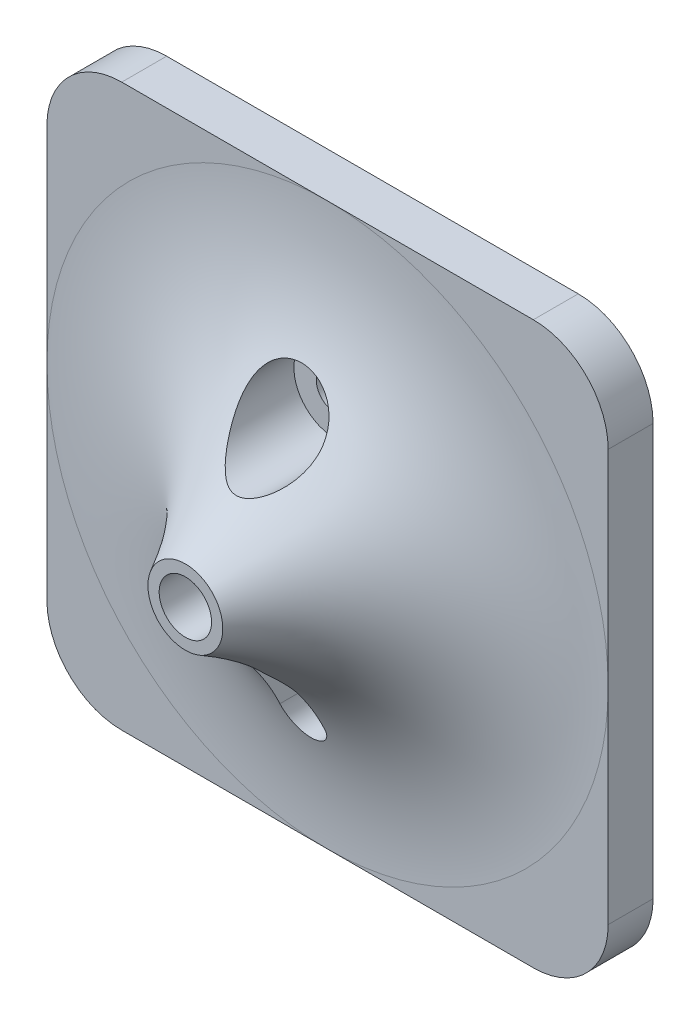
SolidWorks part; units mm, degrees
ref_plane "Front Plane" through (0, 0, 0) normal (0, 0, 1) x (1, 0, 0)
ref_plane "Top Plane" through (0, 0, 0) normal (0, 1, 0) x (1, 0, 0)
ref_plane "Right Plane" through (0, 0, 0) normal (1, 0, 0) x (0, 0, -1)
sketch "Sketch1" plane through (0, 0, 0) normal (0, 0, 1) x (1, 0, 0)
  line L1 (-27.5, 37.5) -> (27.5, 37.5)
  line L2 (-37.5, 27.5) -> (-37.5, -27.5)
  line L3 (-27.5, -37.5) -> (27.5, -37.5)
  line L4 (37.5, 27.5) -> (37.5, -27.5)
  line L5 (-37.5, 37.5) -> (37.5, -37.5) construction
  line L6 (-37.5, -37.5) -> (37.5, 37.5) construction
  arc A0 (-37.5, -27.5) -> (-27.5, -37.5) centre (-27.5, -27.5) ccw
  arc A1 (27.5, -37.5) -> (37.5, -27.5) centre (27.5, -27.5) ccw
  arc A2 (27.5, 37.5) -> (37.5, 27.5) centre (27.5, 27.5) cw
  arc A3 (-27.5, 37.5) -> (-37.5, 27.5) centre (-27.5, 27.5) ccw
  point P0 (0, 0)
  dimension "D3" = 10
  dimension "D1" = 75
  dimension "D2" = 75
extrude "Boss-Extrude1" add sketch "Sketch1" along normal blind 25
sketch "Sketch5" plane through (0, 0, 25) normal (0, 0, 1) x (1, 0, 0)
  circle A0 centre (0, 0) radius 3.5
  dimension "D1" = 7
extrude "Cut-Extrude1" cut sketch "Sketch5" against normal blind 15
sketch "Sketch6" plane through (0, 0, 10) normal (0, 0, 1) x (1, 0, 0)
  circle A0 centre (0, 0) radius 2.5
  dimension "D1" = 5
extrude "Cut-Extrude2" cut sketch "Sketch6" against normal through all
sketch "Sketch7" plane through (0, 0, 0) normal (0, 0, -1) x (-1, 0, 0)
  line L1 (0, -5.1962) -> (4.5, -2.5981)
  line L2 (4.5, -2.5981) -> (4.5, 2.5981)
  line L3 (4.5, 2.5981) -> (0, 5.1962)
  line L4 (0, 5.1962) -> (-4.5, 2.5981)
  line L5 (-4.5, 2.5981) -> (-4.5, -2.5981)
  line L6 (-4.5, -2.5981) -> (0, -5.1962)
  circle A0 centre (0, 0) radius 4.5 construction
  dimension "D1" = 9
extrude "Cut-Extrude3" cut sketch "Sketch7" against normal blind 4
sketch "Sketch3" plane through (0, -37.5, 0) normal (0, -1, 0) x (1, 0, 0)
  line L4 (2, 2) -> (2, 0)
  line L5 (41.25, 0) -> (-41.25, 0) construction
  line L6 (2, 0) -> (-2, 0)
  line L7 (-2, 0) -> (-2, 2)
  arc A1 (2, 2) -> (-2, 2) centre (0, 2) ccw
  dimension "D1" = 4
extrude "Cut-Extrude4" cut sketch "Sketch3" against normal blind 20
sketch "Sketch10" plane through (0, 0, 25) normal (0, 0, 1) x (1, 0, 0)
  circle A0 centre (0, 15) radius 5.5
  dimension "D1" = 11
  dimension "D2" = 15
sketch "Sketch8" plane through (0, 0, 0) normal (0, 1, 0) x (1, 0, 0)
  line L0 (0, 0) -> (0, -50000) construction
  line L1 (37.5, -25) -> (37.5, 0) construction
  line L2 (27.5, -25) -> (-27.5, -25) construction
  line L3 (5, -25) -> (5, -35)
  line L4 (5, -35) -> (67.5, -35)
  line L5 (67.5, -35) -> (67.5, -6)
  line L6 (67.5, -6) -> (37.5, -6)
  line L7 (-41.25, 0) -> (41.25, 0) construction
  spline S0 degree 2 poles (37.5, -6) (15.2106, -5.8474) (5, -25) knots 0 0 0 1 1 1
  dimension "D1" = 30
  dimension "D2" = 10
  dimension "D3" = 5
  dimension "D4" = 6
revolve "Cut-Revolve2" cut sketch "Sketch8" angle 360 about L0
sketch "Sketch9" plane through (0, 0, 0) normal (0, 0, -1) x (-1, 0, 0)
  line L1 (0, -14.5) -> (0, -20.5) construction
  line L2 (3, -14.5) -> (3, -20.5)
  line L3 (-3, -14.5) -> (-3, -20.5)
  line L4 (-2, -17.5) -> (2, -17.5) construction
  arc A1 (3, -14.5) -> (-3, -14.5) centre (0, -14.5) ccw
  arc A2 (-3, -20.5) -> (3, -20.5) centre (0, -20.5) ccw
  point P2 (0, -17.5)
  dimension "D1" = 6
  dimension "D2" = 3
extrude "Cut-Extrude6" cut sketch "Sketch9" against normal up to next
extrude "Cut-Extrude7" cut sketch "Sketch10" against normal blind 20
sketch "Sketch11" plane through (0, 0, 5) normal (0, 0, 1) x (1, 0, 0)
  circle A0 centre (0, 15) radius 5.5 construction
  circle A1 centre (0, 15) radius 5.5 construction
  circle A2 centre (0, 15) radius 2.5
  dimension "D1" = 5
extrude "Cut-Extrude8" cut sketch "Sketch11" against normal through all
chamfer "Chamfer1" distance 1 angle 45 7 edges at (-2.5, 0, 4) (4.5, 0, 4) (2.25, 3.8971, 4) (-2.25, 3.8971, 4) (-4.5, 0, 4) (-2.25, -3.8971, 4) (2.25, -3.8971, 4)
fillet "Fillet1" radius 2 3 edges at (-2, -22.7361, 1) (-0.0378, -23.4998, 3.9996) (2, -22.7361, 1)
